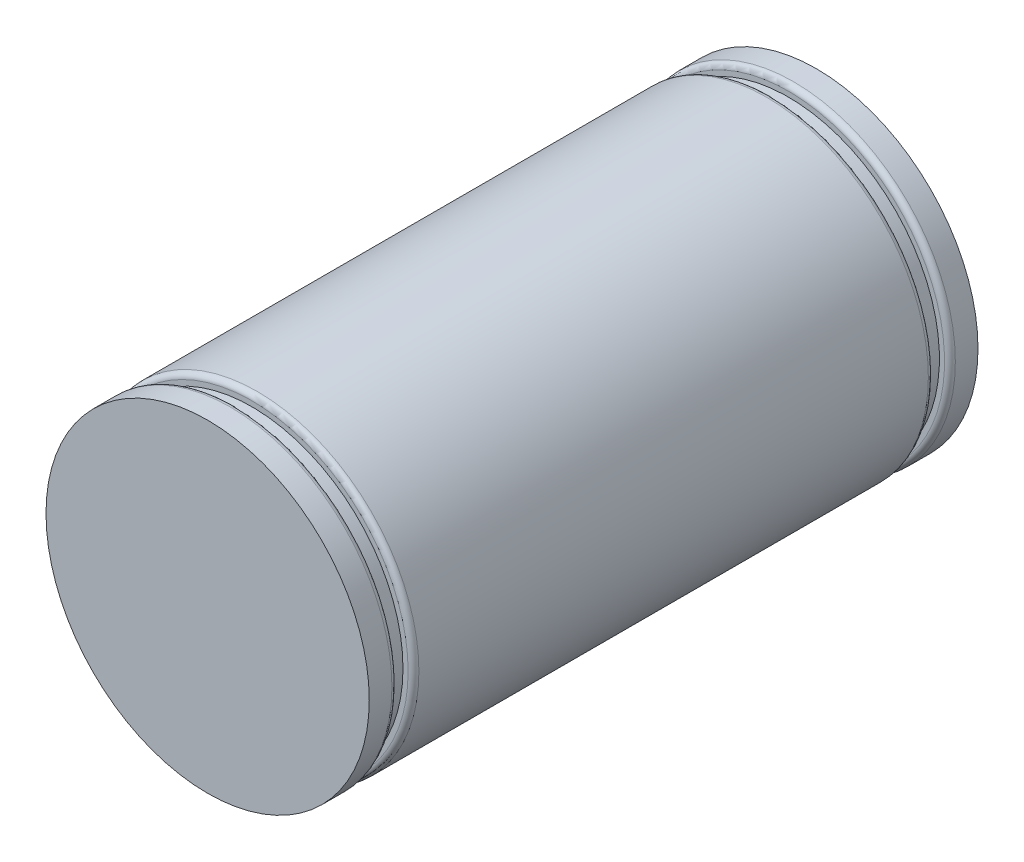
SolidWorks part; units mm, degrees
ref_plane "Front Plane" through (0, 0, 0) normal (0, 0, 1) x (1, 0, 0)
ref_plane "Top Plane" through (0, 0, 0) normal (0, 1, 0) x (1, 0, 0)
ref_plane "Right Plane" through (0, 0, 0) normal (1, 0, 0) x (0, 0, -1)
sketch "Sketch1" plane through (0, 0, 0) normal (0, 0, 1) x (1, 0, 0)
  circle A0 centre (0, 0) radius 14.975
  dimension "D1" = 29.95
extrude "Boss-Extrude1" add sketch "Sketch1" along normal blind 24.1 and the other way blind 24.1
sketch "Sketch2" plane through (0, 0, 24.1) normal (0, 0, 1) x (1, 0, 0)
  circle A0 centre (0, 0) radius 14
  dimension "D1" = 28
extrude "Boss-Extrude2" add sketch "Sketch2" along normal blind 1.5
sketch "Sketch3" plane through (0, 0, 25.6) normal (0, 0, 1) x (1, 0, 0)
  circle A0 centre (0, 0) radius 14.975
  dimension "D1" = 29.95
extrude "Boss-Extrude3" add sketch "Sketch3" along normal blind 2.6
sketch "Sketch4" plane through (0, 0, -24.1) normal (0, 0, -1) x (-1, 0, 0)
  circle A0 centre (0, 0) radius 14
  dimension "D1" = 28
extrude "Boss-Extrude4" add sketch "Sketch4" along normal blind 1.5
sketch "Sketch5" plane through (0, 0, -25.6) normal (0, 0, -1) x (-1, 0, 0)
  circle A0 centre (0, 0) radius 14.975
  dimension "D1" = 29.95
extrude "Boss-Extrude5" add sketch "Sketch5" along normal blind 2.6
fillet "Fillet1" radius 0.5 1 edges at (14.975, 0, 25.6)
fillet "Fillet3" radius 0.5 3 edges at (-14.975, 0, -25.6) (14.975, 0, -24.1) (14.975, 0, 24.1)
